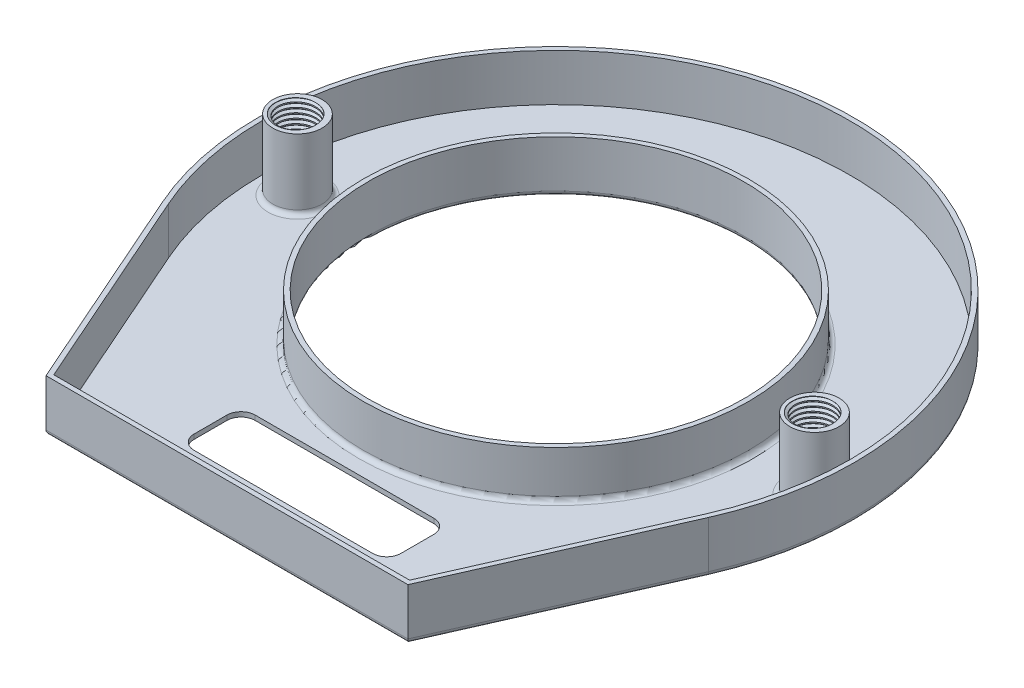
SolidWorks part; units mm, degrees
ref_plane "Front Plane" through (0, 0, 0) normal (0, 0, 1) x (1, 0, 0)
ref_plane "Top Plane" through (0, 0, 0) normal (0, 1, 0) x (1, 0, 0)
ref_plane "Right Plane" through (0, 0, 0) normal (1, 0, 0) x (0, 0, -1)
sketch "Sketch1" plane through (0, 0, 0) normal (0, 1, 0) x (1, 0, 0)
  line L0 (0, 0) -> (0, 8.4709) construction
  line L6 (0, 0) -> (-38.5, 0)
  line L7 (0, 0) -> (38.5, 0)
  line L10 (-19, 25) -> (19, 25)
  line L11 (-38.5, 0) -> (-58.0863, 44.3439)
  line L12 (38.5, 0) -> (58.0863, 44.3439)
  line L13 (-22, 22) -> (-22, 15)
  line L14 (-19, 12) -> (19, 12)
  line L15 (22, 22) -> (22, 15)
  circle A2 centre (0, 70) radius 40
  arc A12 (58.0863, 44.3439) -> (-58.0863, 44.3439) centre (0, 70) ccw
  circle A13 centre (-55, 70) radius 4
  circle A14 centre (55, 70) radius 4
  arc A15 (-19, 12) -> (-22, 15) centre (-19, 15) cw
  arc A16 (19, 12) -> (22, 15) centre (19, 15) ccw
  arc A17 (22, 22) -> (19, 25) centre (19, 22) ccw
  arc A18 (-19, 25) -> (-22, 22) centre (-19, 22) ccw
  point P17 (0, 12)
  point P22 (22, 12)
  point P25 (22, 25)
  point P28 (-22, 25)
  dimension "D2" = 8
  dimension "D3" = 80
  dimension "D7" = 44
  dimension "D9" = 38.5
  dimension "D11" = 3
  dimension "D4" = 127
  dimension "D5" = 70
  dimension "D6" = 55
  dimension "D8" = 13
  dimension "D10" = 38.5
  dimension "D12" = 12
extrude "Boss-Extrude1" add sketch "Sketch1" along normal blind 1
sketch "Sketch2" plane through (0, 1, 0) normal (0, 1, 0) x (1, 0, 0)
  line L3 (-58.0863, 44.3439) -> (-38.5, 0)
  line L4 (-38.5, 0) -> (38.5, 0)
  line L5 (38.5, 0) -> (58.0863, 44.3439)
  line L6 (-57.1715, 44.7479) -> (-37.8485, 1)
  line L7 (-37.8485, 1) -> (37.8485, 1)
  line L8 (37.8485, 1) -> (57.1715, 44.7479)
  line L9 (-57.1715, 44.7479) -> (-37.8485, 1)
  line L10 (-37.8485, 1) -> (37.8485, 1)
  line L11 (37.8485, 1) -> (57.1715, 44.7479)
  arc A1 (58.0863, 44.3439) -> (-58.0863, 44.3439) centre (0, 70) ccw
  arc A2 (57.1715, 44.7479) -> (-57.1715, 44.7479) centre (0, 70) ccw
  arc A3 (57.1715, 44.7479) -> (-57.1715, 44.7479) centre (0, 70) ccw
  circle A4 centre (0, 70) radius 40
  circle A5 centre (0, 70) radius 41
  line M6 (-58.0863, 44.3439) -> (-38.5, 0)
  line M7 (-38.5, 0) -> (38.5, 0)
  line M8 (38.5, 0) -> (58.0863, 44.3439)
  arc M9 (58.0863, 44.3439) -> (-58.0863, 44.3439) centre (0, 70) ccw
  circle M10 centre (0, 70) radius 40
  dimension "D1" = 1
  dimension "D2" = 1
  dimension "D3" = 1
extrude "Boss-Extrude2" add sketch "Sketch2" along normal blind 10 contours A5 M10 | A3 L11 L10 L9 M9 M6 M7 M8 region at (0, 1, -133.3157) region at (-40.884, 1, -70)
fillet "Fillet1" radius 1 6 edges at (48.2931, 0, -22.1719) (0, 0, -133.5) (0, 0, -30) (-48.2931, 0, -22.1719) (0, 0, 0) (0, 1, -29)
sketch "Sketch3" plane through (0, 1, 0) normal (0, 1, 0) x (1, 0, 0)
  circle A0 centre (-55, 70) radius 4
  circle A1 centre (-55, 70) radius 5.25
  circle A2 centre (55, 70) radius 4
  circle A3 centre (55, 70) radius 5.25
  dimension "D1" = 8
  dimension "D2" = 10.5
extrude "Boss-Extrude3" add sketch "Sketch3" along normal blind 15
fillet "Fillet2" radius 1 2 edges at (55, 1, -64.75) (-55, 1, -64.75)
thread "Thread1" pitch 1 method cut profile "Thread Profile1" start angle 0, offset 1, length 20, pitch 1, diameter 8
ref_plane "Plane1" through (-51, -1, -70) normal (0, 0, 1) x (1, 0, 0)
sketch "Thread Profile1" plane through (-51, -1, -70) normal (0, 0, 1) x (1, 0, 0)
  line L0 (0, 0) -> (0, 1) construction
  line L1 (0, 0) -> (0.5413, 0.3125)
  line L2 (0.5413, 0.3125) -> (0.5413, 0.4375)
  line L3 (0.5413, 0.4375) -> (0, 0.75)
  line L4 (0.5413, 0.375) -> (0, 0.375) construction
  line L11 (0, 0) -> (0, 0.75)
  point P2 (0, 0)
  dimension "Pitch" = 1
  dimension "Profile_Angle" = 60
  dimension "Profile_Land" = 0.125
  dimension "Profile_Height" = 0.5413
thread "Thread2" pitch 1 method cut profile "Thread Profile2" start angle 0, offset 1, length 20, pitch 1, diameter 8
ref_plane "Plane2" through (59, -1, -70) normal (0, 0, 1) x (1, 0, 0)
sketch "Thread Profile2" plane through (59, -1, -70) normal (0, 0, 1) x (1, 0, 0)
  line L0 (0, 0) -> (0, 1) construction
  line L1 (0, 0) -> (0.5413, 0.3125)
  line L2 (0.5413, 0.3125) -> (0.5413, 0.4375)
  line L3 (0.5413, 0.4375) -> (0, 0.75)
  line L4 (0.5413, 0.375) -> (0, 0.375) construction
  line L11 (0, 0) -> (0, 0.75)
  point P2 (0, 0)
  dimension "Pitch" = 1
  dimension "Profile_Angle" = 60
  dimension "Profile_Land" = 0.125
  dimension "Profile_Height" = 0.5413
